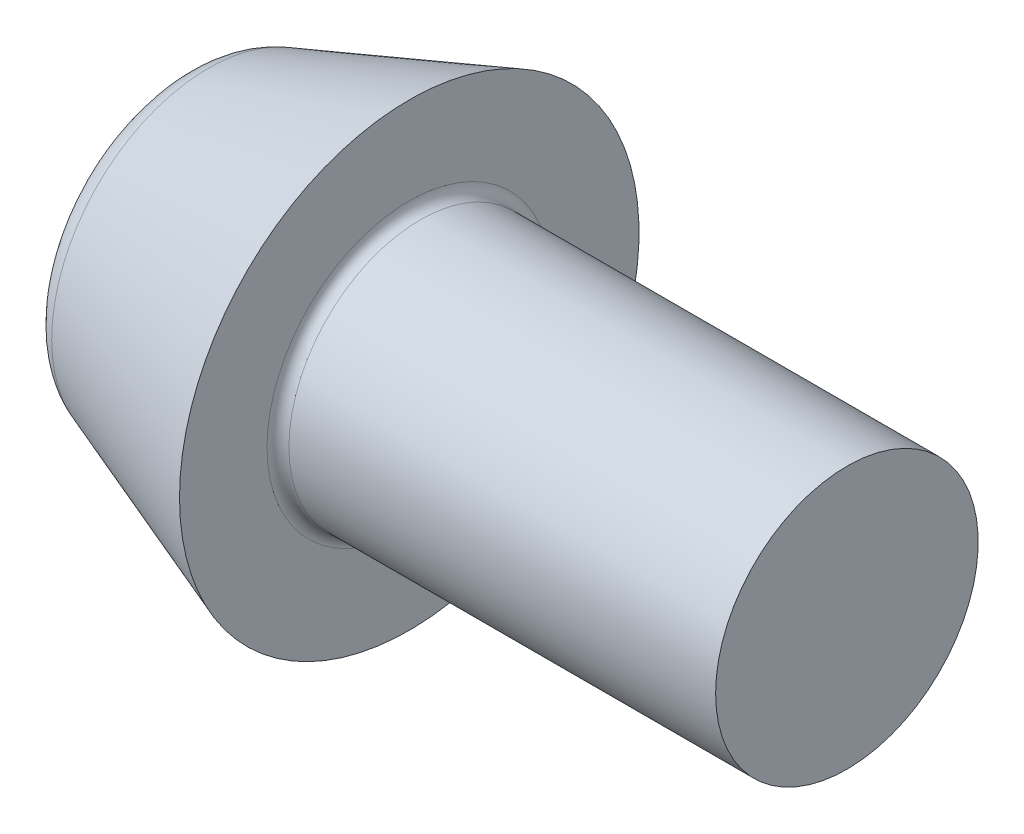
SolidWorks part; units mm, degrees
ref_plane "Front" through (0, 0, 0) normal (0, 0, 1) x (1, 0, 0)
ref_plane "Top" through (0, 0, 0) normal (0, 1, 0) x (1, 0, 0)
ref_plane "Right" through (0, 0, 0) normal (1, 0, 0) x (0, 0, -1)
sketch "Sketch1" plane through (0, 0, 0) normal (0, 0, 1) x (1, 0, 0)
  line L0 (0, 0) -> (30.5, 0)
  line L1 (30.5, 0) -> (30.5, 6)
  line L2 (30.5, 6) -> (10.5, 6)
  line L3 (10.5, 6) -> (10.5, 10.5)
  line L4 (10.5, 10.5) -> (0, 6.6783)
  line L5 (0, 6.6783) -> (0, 0)
  line L6 (-26.4886, 0) -> (67.8543, 0) construction
  line L7 (-6.0327, 10.5) -> (19.105, 10.5) construction
  dimension "D1" = 20
  dimension "L" = 20
  dimension "d" = 12
  dimension "K" = 10.5
  dimension "dk" = 21
revolve "Base-Revolve" add sketch "Sketch1" angle 360 about L6
fillet "Fillet1" radius 0.5 1 edges at (10.5, 0, 6)
fillet "Fillet2" radius 2 1 edges at (0, 0, 6.6783)
